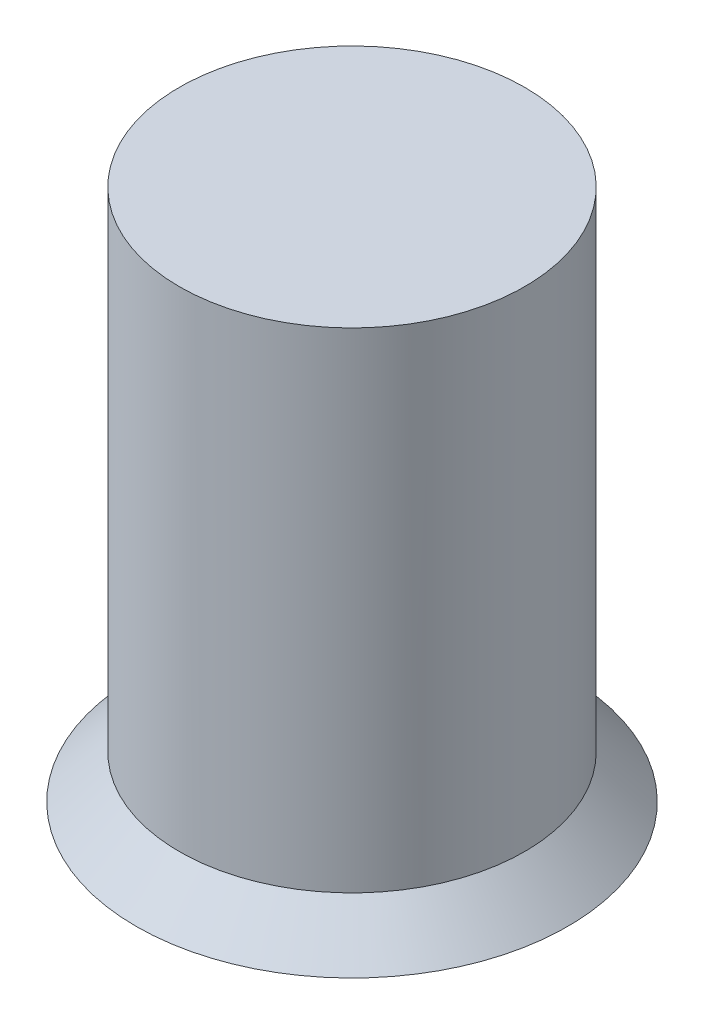
SolidWorks part; units mm, degrees
ref_plane "Plan de face" through (0, 0, 0) normal (0, 0, 1) x (1, 0, 0)
ref_plane "Plan de dessus" through (0, 0, 0) normal (0, 1, 0) x (1, 0, 0)
ref_plane "Plan de droite" through (0, 0, 0) normal (1, 0, 0) x (0, 0, -1)
sketch "Esquisse1" plane through (0, 0, 0) normal (0, 1, 0) x (1, 0, 0)
  circle A0 centre (0, 0) radius 15
extrude "Boss.-Extru.1" add sketch "Esquisse1" along normal blind 3
chamfer "Chanfrein1" distance 3 angle 45 1 edges at (0, 3, 15)
sketch "Esquisse2" plane through (0, 3, 0) normal (0, 1, 0) x (1, 0, 0)
  circle A1 centre (0, 0) radius 12
  circle A2 centre (0, 0) radius 12
  dimension "D1" = 0
extrude "Boss.-Extru.2" add sketch "Esquisse2" along normal blind 34
